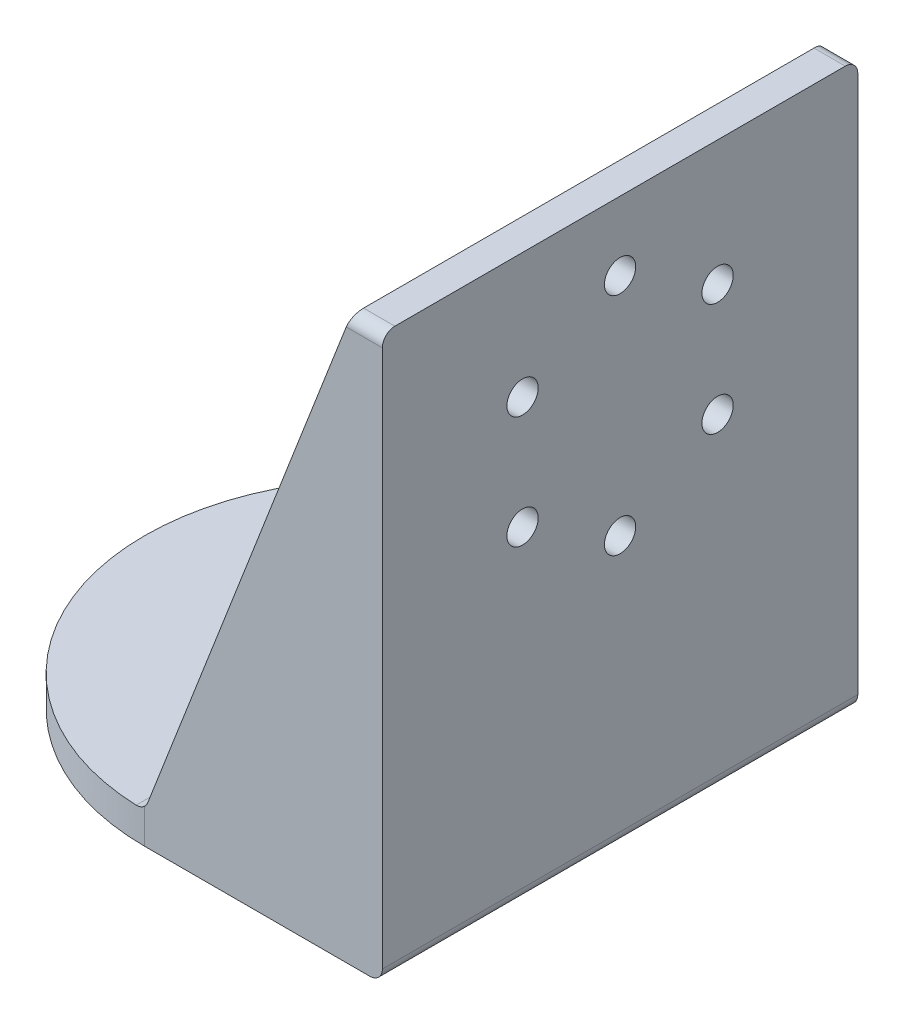
SolidWorks part; units mm, degrees
ref_plane "Спереди" through (0, 0, 0) normal (0, 0, 1) x (1, 0, 0)
ref_plane "Сверху" through (0, 0, 0) normal (0, 1, 0) x (1, 0, 0)
ref_plane "Справа" through (0, 0, 0) normal (1, 0, 0) x (0, 0, -1)
sketch "Эскиз3" plane through (0, 0, 0) normal (0, 0, 1) x (1, 0, 0)
  line L1 (76, 0) -> (0, 0)
  line L3 (71, 5) -> (0, 5)
  line L4 (0, 0) -> (0, 5)
  line L8 (76, 0) -> (76, 90)
  line L9 (76, 90) -> (71, 90)
  line L10 (71, 5) -> (71, 90)
  point P0 (0, 0)
  dimension "D1" = 5
  dimension "D2" = 76
  dimension "D3" = 5
  dimension "D4" = 90
extrude "Бобышка-Вытянуть1" add sketch "Эскиз3" along normal blind 76
fillet "Скругление1" radius 38 2 edges at (0, 2.5, 0) (0, 2.5, 76)
ref_plane "Плоскость7" through (0, 0, 0) normal (0, 0, -1) x (-1, 0, 0)
ref_plane "Плоскость8" through (0, 0, 76) normal (0, 0, 1) x (1, 0, 0)
sketch "Эскиз4" plane through (0, 0, 76) normal (0, 0, 1) x (1, 0, 0)
  line L0 (71, 90) -> (38, 5)
rib "Ребро1" sketch "Эскиз4" sketch "Эскиз4" thickness 5 extrusion direction parallel to sketch draft on no parameters "D1"=5
sketch "Эскиз5" plane through (0, 0, 0) normal (0, 0, -1) x (-1, 0, 0)
  line L0 (-71, 90) -> (-38, 5)
rib "Ребро2" sketch "Эскиз5" sketch "Эскиз5" thickness 5 extrusion direction parallel to sketch draft on no parameters "D1"=5
sketch "Эскиз7" plane through (0, 5, 0) normal (0, 1, 0) x (1, 0, 0)
  line L0 (38, -38) -> (20, -38) construction
  circle A0 centre (38, -38) radius 18 construction
  circle A1 centre (20, -38) radius 2.5
  circle A2 centre (38, -38) radius 18
  circle A3 centre (29, -22.4115) radius 2.5
  circle A4 centre (38, -38) radius 18
  circle A5 centre (47, -22.4115) radius 2.5
  circle A6 centre (38, -38) radius 18
  circle A7 centre (56, -38) radius 2.5
  circle A8 centre (38, -38) radius 18
  circle A9 centre (47, -53.5885) radius 2.5
  circle A10 centre (38, -38) radius 18
  circle A11 centre (29, -53.5885) radius 2.5
  dimension "D1" = 36
  dimension "D2" = 5
  dimension "D3" = 6
extrude "Вырез-Вытянуть1" cut sketch "Эскиз7" against normal blind 10 contours A1 | A3 | A5 | A7 | A9 | A11
sketch "Эскиз8" plane through (76, 0, 0) normal (1, 0, 0) x (0, 0, -1)
  line L0 (-76, 0) -> (0, 0) construction
  line L1 (0, 0) -> (0, 90) construction
  line L2 (-38, 61) -> (-38, 43) construction
  circle A0 centre (-38, 61) radius 18 construction
  circle A1 centre (-38, 43) radius 2.5
  circle A2 centre (-38, 61) radius 18
  circle A3 centre (-53.5885, 52) radius 2.5
  circle A4 centre (-38, 61) radius 18
  circle A5 centre (-53.5885, 70) radius 2.5
  circle A6 centre (-38, 61) radius 18
  circle A7 centre (-38, 79) radius 2.5
  circle A8 centre (-38, 61) radius 18
  circle A9 centre (-22.4115, 70) radius 2.5
  circle A10 centre (-38, 61) radius 18
  circle A11 centre (-22.4115, 52) radius 2.5
  dimension "D1" = 36
  dimension "D2" = 61
  dimension "D4" = 5
  dimension "D3" = 38
  dimension "D5" = 6
extrude "Вырез-Вытянуть2" cut sketch "Эскиз8" against normal blind 10 contours A5 | A7 | A9 | A11 | A1 | A3
fillet "Скругление2" radius 2 1 edges at (76, 0, 38)
chamfer "Фаска1" distance 10 distance2 5 1 edges at (71, 5, 38) first distance on face at (71, 52, 51.0885)
fillet "Скругление3" radius 2 2 edges at (38, 5, 73.5) (38, 5, 2.5)
fillet "Скругление4" radius 2 2 edges at (73.5, 90, 0) (73.5, 90, 76)
